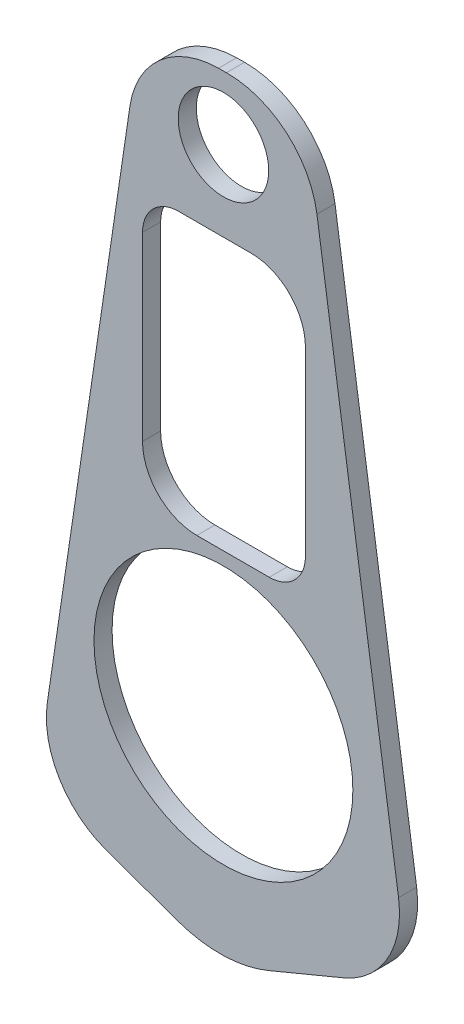
SolidWorks part; units mm, degrees
ref_plane "Front" through (0, 0, 0) normal (0, 0, 1) x (1, 0, 0)
ref_plane "Top" through (0, 0, 0) normal (0, 1, 0) x (1, 0, 0)
ref_plane "Right" through (0, 0, 0) normal (1, 0, 0) x (0, 0, -1)
sketch "Sketch3" plane through (0, 0, 0) normal (0, 0, 1) x (1, 0, 0)
  line L4 (826.0027, 512.1195) -> (1217.7274, 371.9099)
  line L10 (1722.5182, 384.6718) -> (2137.4103, 557.2912)
  line L19 (1445.2877, 4562.7081) -> (1489.1209, 4563.1772)
  line L20 (956.0341, 4135.9897) -> (499.8941, 1056.1261)
  line L21 (1989.0771, 4136.4588) -> (2439.9466, 1092.1822)
  line L23 (1325.6845, 2267.8735) -> (1725.6845, 2267.8735)
  line L24 (1025.6845, 2567.8735) -> (1025.6845, 3567.8735)
  line L25 (1225.6845, 3767.8735) -> (1625.6845, 3767.8735)
  line L26 (1925.6845, 2467.8735) -> (1925.6845, 3467.8735)
  line L27 (1025.6845, 2267.8735) -> (1925.6845, 3767.8735) construction
  line L28 (1025.6845, 3767.8735) -> (1925.6845, 2267.8735) construction
  circle A13 centre (1472.5904, 4210.9524) radius 250
  circle A18 centre (1472.5904, 1480.6871) radius 715
  arc A19 (1025.6845, 3567.8735) -> (1225.6845, 3767.8735) centre (1225.6845, 3567.8735) cw
  arc A20 (1725.6845, 2267.8735) -> (1925.6845, 2467.8735) centre (1725.6845, 2467.8735) ccw
  arc A21 (1925.6845, 3467.8735) -> (1625.6845, 3767.8735) centre (1625.6845, 3467.8735) ccw
  arc A22 (1325.6845, 2267.8735) -> (1025.6845, 2567.8735) centre (1325.6845, 2567.8735) cw
  arc A23 (826.0027, 512.1195) -> (499.8941, 1056.1261) centre (994.499, 982.8732) cw
  arc A24 (2137.4103, 557.2912) -> (2439.9466, 1092.1822) centre (1945.3417, 1018.9293) ccw
  arc A25 (1722.5182, 384.6718) -> (1217.7274, 371.9099) centre (1453.6223, 1030.965) cw
  arc A26 (956.0341, 4135.9897) -> (1445.2877, 4562.7081) centre (1450.639, 4062.7367) cw
  arc A27 (1989.0771, 4136.4588) -> (1489.1209, 4563.1772) centre (1494.4722, 4063.2059) ccw
  point P5 (1475.6845, 3017.8735)
  point P14 (1472.5904, 3061.0563)
  point P28 (-342.5123, 4804.3525)
  point P33 (3145.1075, 4804.3525)
  point P35 (1472.5904, 280.6871)
  dimension "D4" = 500
  dimension "D5" = 1430
  dimension "D6" = 500
  dimension "D7" = 200
  dimension "D8" = 200
  dimension "D9" = 300
  dimension "D11" = 500
  dimension "D2" = 1500
  dimension "D1" = 900
  dimension "D3" = 500
  dimension "D10" = 300
  dimension "D12" = 500
  dimension "D13" = 700
  dimension "D14" = 500
  dimension "D15" = 500
extrude "Boss-Extrude2" add sketch "Sketch3" along normal blind 100
